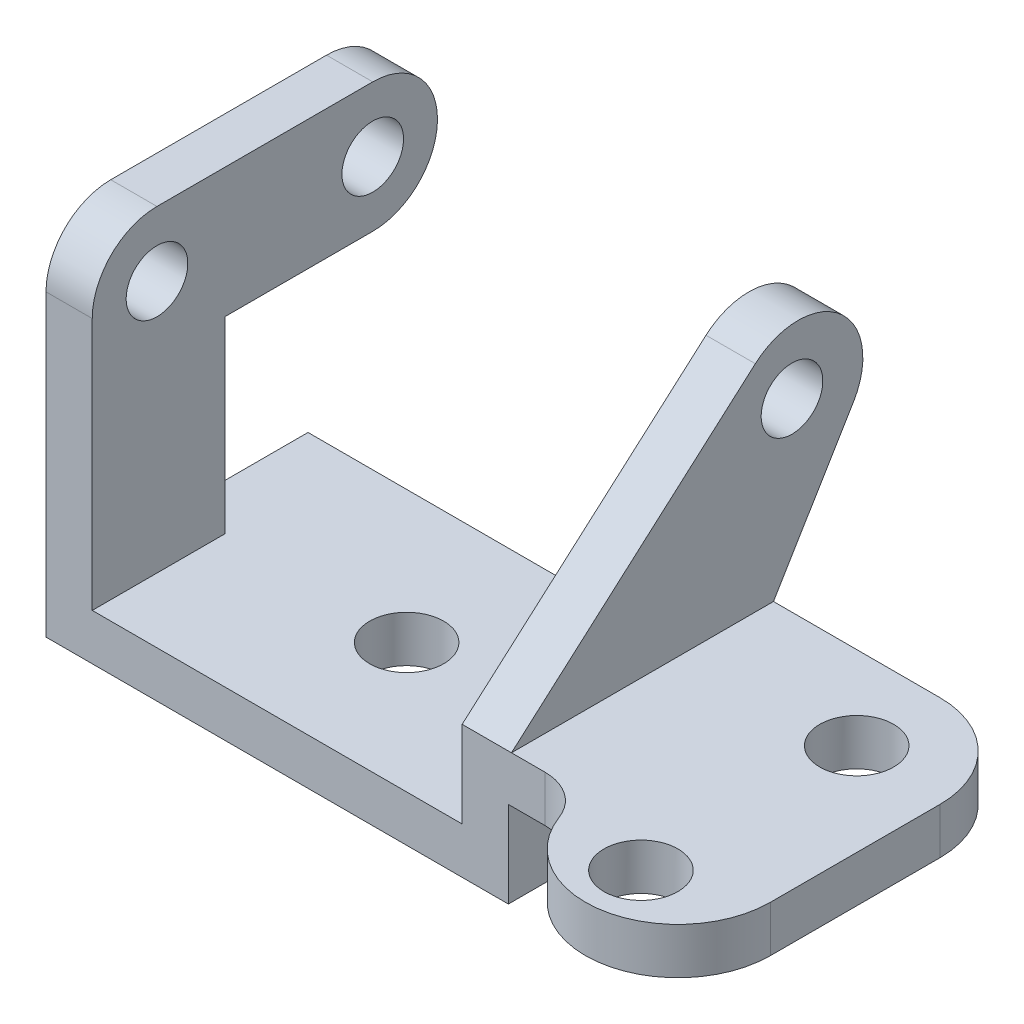
SolidWorks part; units mm, degrees
material "AISI 304"
ref_plane "Front Plane" through (0, 0, 0) normal (0, 0, 1) x (1, 0, 0)
ref_plane "Top Plane" through (0, 0, 0) normal (0, 1, 0) x (1, 0, 0)
ref_plane "Right Plane" through (0, 0, 0) normal (1, 0, 0) x (0, 0, -1)
sketch "Sketch1" plane through (0, 0, 0) normal (0, 0, 1) x (1, 0, 0)
  line L0 (0, 0) -> (150, 0)
  line L1 (150, 0) -> (150, 28)
  line L2 (150, 28) -> (235, 28)
  dimension "D1" = 150
  dimension "D2" = 28
  dimension "D3" = 85
extrude "Extrude-Thin1" add sketch "Sketch1" against normal blind 85 thin thin type one direction reverse wall 15
sketch "Sketch2" plane through (0, 0, 0) normal (-1, 0, 0) x (0, 0, 1)
  line L0 (0, 15) -> (0, 118)
  line L1 (0, 118) -> (-112, 118)
  line L2 (-112, 118) -> (-112, 76)
  line L3 (-112, 76) -> (-43, 76)
  line L4 (-43, 76) -> (-43, 15)
  line L5 (-85, 15) -> (0, 15) construction
  line L6 (-43, 15) -> (0, 15)
  line L7 (-85, 0) -> (-85, 15) construction
  line L8 (-112, 97) -> (-53.7993, 97) construction
  line L9 (-85, 15) -> (0, 15) construction
  dimension "D1" = 42
  dimension "D2" = 82
  dimension "D3" = 112
  dimension "D4" = 42
extrude "Boss-Extrude1" add sketch "Sketch2" against normal blind 15
sketch "Sketch3" plane through (135, 0, 0) normal (-1, 0, 0) x (0, 0, 1)
  line L0 (0, 43) -> (-79.1119, 112.7518)
  line L1 (-110.9908, 86.168) -> (-85, 43)
  line L2 (-85, 15) -> (0, 15) construction
  line L3 (-85, 15) -> (-85, 43) construction
  line L8 (0, 15) -> (0, 43)
  line L9 (0, 43) -> (-85, 43)
  line L10 (-85, 43) -> (-85, 15)
  line L11 (-85, 15) -> (0, 15)
  line L13 (0, 43) -> (-85, 43)
  arc A0 (-79.1119, 112.7518) -> (-110.9908, 86.168) centre (-93, 97) ccw
  dimension "D2" = 21
  dimension "D1" = 82
  dimension "D3" = 8
  dimension "D4" = 0
extrude "Boss-Extrude2" add sketch "Sketch3" against normal blind 16
fillet "Fillet1" radius 21 3 edges at (7.5, 76, -112) (7.5, 118, -112) (7.5, 118, 0)
sketch "Sketch5" plane through (0, 43, 0) normal (0, 1, 0) x (1, 0, 0)
  line L0 (151, 0) -> (235, 0) construction
  line L1 (175, 0) -> (235, 0)
  arc A0 (235, 0) -> (175, 0) centre (205, 0) cw
  dimension "D1" = 30
extrude "Boss-Extrude3" add sketch "Sketch5" against normal up to surface (15 mm away) up to face at (192.5, 28, -42.5)
fillet "Fillet2" radius 16 1 edges at (175, 35.5, 0)
sketch "Sketch6" plane through (0, 43, 0) normal (0, 1, 0) x (1, 0, 0)
  line L0 (151, 0) -> (161.8723, 0) construction
  line L1 (135, 85) -> (135, 0) construction
  circle A0 centre (205, -12) radius 12
  circle A1 centre (205, 58) radius 12
  dimension "D2" = 24
  dimension "D1" = 70
  dimension "D3" = 58
  dimension "D4" = 70
extrude "Cut-Extrude2" cut sketch "Sketch6" against normal through all
fillet "Fillet3" radius 30 1 edges at (235, 35.5, -85)
sketch "Sketch7" plane through (0, 15, 0) normal (0, 1, 0) x (1, 0, 0)
  line L0 (15, 0) -> (135, 0) construction
  circle A0 centre (75, 42) radius 12
  dimension "D1" = 75
  dimension "Hole_1" = 24
  dimension "D2" = 42
extrude "Cut-Extrude3" cut sketch "Sketch7" against normal through all
sketch "Sketch9" plane through (0, 0, 0) normal (-1, 0, 0) x (0, 0, 1)
  circle A0 centre (-91, 97) radius 10
  arc A1 (-112, 97) -> (-91, 76) centre (-91, 97) ccw construction
  circle A2 centre (-21, 97) radius 10
  dimension "D1" = 20
  dimension "D2" = 70
extrude "Cut-Extrude4" cut sketch "Sketch9" against normal through all
